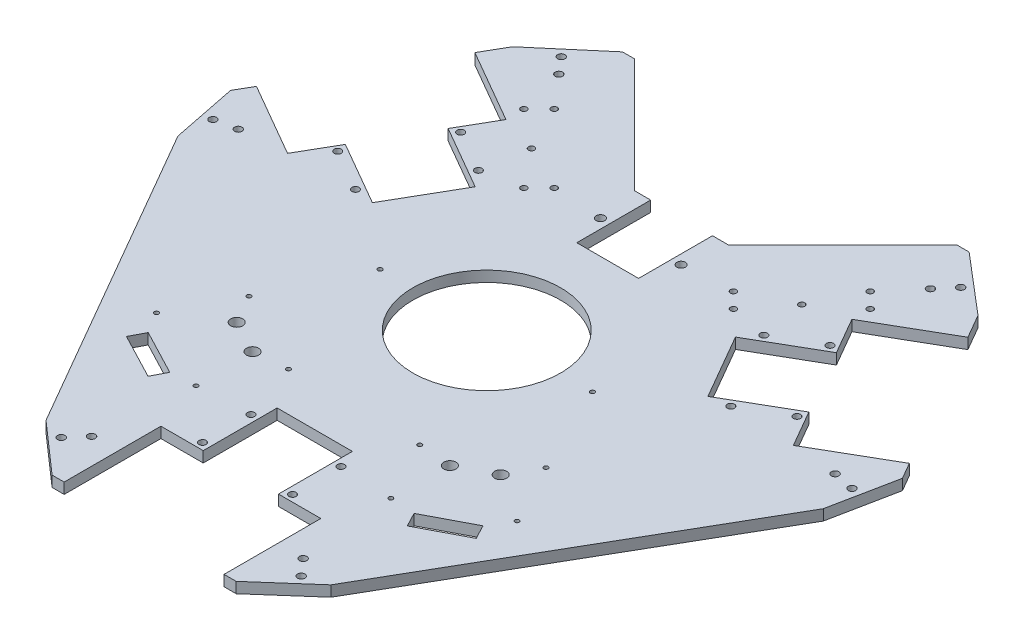
SolidWorks part; units mm, degrees
note: '?' marks a value the reader was unsure of.
material "1060 合金"
ref_plane "前视基准面" through (0, 0, 0) normal (0, 0, 1) x (1, 0, 0)
ref_plane "上视基准面" through (0, 0, 0) normal (0, 1, 0) x (1, 0, 0)
ref_plane "右视基准面" through (0, 0, 0) normal (1, 0, 0) x (0, 0, -1)
sketch "草图1" plane through (0, 0, 0) normal (0, 1, 0) x (1, 0, 0)
  line L1 (0, 0) -> (0, 227.8132) construction
  line L6 (0, 0) -> (-213.2068, 123.095) construction
  line L16 (-173.1806, 192.4224) -> (-250, 59.3672)
  line L17 (-250, 59.3672) -> (-68.5, -255) construction
  line L19 (250, 59.3672) -> (68.5, -255) construction
  line L20 (173.1806, 192.4224) -> (250, 59.3672)
  line L21 (-129, 230) -> (129, 230)
  line L22 (-250, 59.3672) -> (-240.171, 10.3428)
  line L23 (-250, -255) -> (250, -255) construction
  line L24 (-250, -255) -> (-250, 245) construction
  line L25 (-250, 245) -> (250, 245) construction
  line L26 (250, -255) -> (250, 245) construction
  line L27 (-250, -255) -> (250, 245) construction
  line L28 (-250, 245) -> (250, -255) construction
  line L29 (-240.171, 10.3428) -> (-106.0418, -221.9756)
  line L30 (-68.5, -255) -> (-106.0418, -221.9756)
  line L31 (68.5, -255) -> (106.0418, -221.9756)
  line L32 (240.171, 10.3428) -> (106.0418, -221.9756)
  line L33 (250, 59.3672) -> (240.171, 10.3428)
  line L34 (-173.1806, 192.4224) -> (-129, 230)
  line L35 (173.1806, 192.4224) -> (129, 230)
  line L36 (0, 0) -> (0, 164.1465) construction
  line L37 (-144.4826, 115.7487) -> (-128.7326, 143.0285) construction
  line L38 (-188.2326, 39.9715) -> (-242.9568, 71.5665) construction
  line L39 (-188.2326, 39.9715) -> (-172.4826, 67.2513) construction
  line L40 (-242.9568, 71.5665) -> (-183.4568, 174.6235) construction
  line L41 (-128.7326, 143.0285) -> (-183.4568, 174.6235) construction
  line L42 (-188.2326, 39.9715) -> (-183.4568, 174.6235) construction
  line L43 (-242.9568, 71.5665) -> (-128.7326, 143.0285) construction
  line L44 (-124.8513, 39.7513) -> (-172.4826, 67.2513) construction
  line L45 (-124.8513, 39.7513) -> (-96.8513, 88.2487) construction
  line L46 (-178.0961, 171.5285) -> (-237.5961, 68.4715) construction
  line L47 (-96.8513, 88.2487) -> (-144.4826, 115.7487) construction
  line L48 (-124.8513, 39.7513) -> (-144.4826, 115.7487) construction
  line L49 (-172.4826, 67.2513) -> (-96.8513, 88.2487) construction
  line L53 (-68.5, -255) -> (68.5, -255)
  circle A0 centre (0, 0) radius 55
  point P9 (-185.8447, 107.2975)
  point P10 (-134.667, 77.75)
  point P21 (0, 0)
  point P24 (0, 0)
  point P29 (0, -5)
  point P63 (0, 0)
  dimension "D10" = 110
  dimension "D2" = 5
  dimension "D3" = 258
  dimension "D4" = 119
  dimension "D6" = 230
  dimension "D7" = 500
  dimension "D8" = 16
  dimension "D9" = 60
  dimension "D11" = 63.19
  dimension "D12" = 55
  dimension "D5" = 128
  dimension "D13" = 56
  dimension "D14" = 60
  dimension "D15" = 57
  dimension "D16" = 137
  dimension "D17" = 255
  dimension "D18" = 246.19
  dimension "D19" = 50
  dimension "D20" = 58
extrude "凸台-拉伸1" add sketch "草图1" along normal blind 8
ref_axis "基准轴1" through (0, 0, 0) along (0, 1, 0)?
sketch "草图34" plane through (0, 8, 0) normal (0, 1, 0) x (1, 0, 0)
  line L0 (0, 0) -> (-213.2068, 123.095) construction
  line L1 (-173.1806, 192.4224) -> (-250, 59.3672) construction
  line L2 (0, 0) -> (0, 102.0762) construction
  line L3 (-144.4826, 115.7487) -> (-128.7326, 143.0285)
  line L4 (-188.2326, 39.9715) -> (-242.9568, 71.5665)
  line L5 (-188.2326, 39.9715) -> (-172.4826, 67.2513)
  line L6 (-242.9568, 71.5665) -> (-183.4568, 174.6235)
  line L7 (-128.7326, 143.0285) -> (-183.4568, 174.6235)
  line L8 (-188.2326, 39.9715) -> (-183.4568, 174.6235) construction
  line L9 (-242.9568, 71.5665) -> (-128.7326, 143.0285) construction
  line L11 (-124.8513, 39.7513) -> (-172.4826, 67.2513)
  line L12 (-124.8513, 39.7513) -> (-96.8513, 88.2487)
  line L13 (172.4826, 67.2513) -> (188.2326, 39.9715)
  line L14 (-96.8513, 88.2487) -> (-144.4826, 115.7487)
  line L15 (-124.8513, 39.7513) -> (-144.4826, 115.7487) construction
  line L16 (-172.4826, 67.2513) -> (-96.8513, 88.2487) construction
  line L17 (128.7326, 143.0285) -> (183.4568, 174.6235)
  line L18 (128.7326, 143.0285) -> (144.4826, 115.7487)
  line L19 (183.4568, 174.6235) -> (242.9568, 71.5665)
  line L20 (188.2326, 39.9715) -> (242.9568, 71.5665)
  line L21 (96.8513, 88.2487) -> (144.4826, 115.7487)
  line L22 (96.8513, 88.2487) -> (124.8513, 39.7513)
  line L23 (124.8513, 39.7513) -> (172.4826, 67.2513)
  line L24 (0, 0) -> (213.2068, 123.095) construction
  line L25 (128.7326, 143.0285) -> (242.9568, 71.5665) construction
  line L26 (183.4568, 174.6235) -> (188.2326, 39.9715) construction
  line L27 (96.8513, 88.2487) -> (172.4826, 67.2513) construction
  line L28 (144.4826, 115.7487) -> (124.8513, 39.7513) construction
  line L29 (-28, -183) -> (-59.5, -183)
  line L30 (59.5, -183) -> (59.5, -255)
  line L31 (59.5, -183) -> (28, -183)
  line L32 (59.5, -246.19) -> (-59.5, -246.19) construction
  line L33 (-59.5, -183) -> (-59.5, -255)
  line L34 (28, -128) -> (28, -183)
  line L35 (28, -128) -> (-28, -128)
  line L36 (-28, -128) -> (-28, -183)
  line L37 (0, 0) -> (0, -246.19) construction
  line L38 (59.5, -183) -> (-59.5, -246.19) construction
  line L39 (59.5, -246.19) -> (-59.5, -183) construction
  line L40 (28, -128) -> (-28, -183) construction
  line L41 (28, -183) -> (-28, -128) construction
  line L43 (-59.5, -255) -> (59.5, -255)
  line L44 (-68.5, -255) -> (68.5, -255) construction
  point P7 (-185.8447, 107.2975)
  point P10 (-134.667, 77.75)
  point P18 (185.8447, 107.2975)
  point P19 (134.667, 77.75)
  point P33 (0, -214.595)
  point P34 (0, -155.5)
  point P43 (0, 0)
  dimension "D1" = 60
  dimension "D2" = 183
  dimension "D3" = 119
  dimension "D4" = 55
  dimension "D5" = 56
  dimension "D6" = 3
extrude "切除-拉伸7" cut sketch "草图34" against normal through all
sketch "草图36" plane through (0, 8, 0) normal (0, 1, 0) x (1, 0, 0)
  line L0 (-63, 0) -> (-116.2089, 30.7202)
  line L1 (-63, 0) -> (-31.5, 54.5596) construction
  line L2 (-108.7089, 43.7106) -> (-92.2089, 72.2894)
  line L3 (-31.5, 54.5596) -> (-84.7089, 85.2798)
  line L4 (-63, 0) -> (-84.7089, 85.2798) construction
  line L5 (-116.2089, 30.7202) -> (-31.5, 54.5596) construction
  line L6 (-108.7089, 43.7106) -> (-60.9051, 16.111)
  line L7 (-108.7089, 43.7106) -> (-92.2089, 72.2894)
  line L8 (-60.9051, 16.111) -> (-44.4051, 44.6899) construction
  line L9 (-92.2089, 72.2894) -> (-44.4051, 44.6899)
  line L10 (-108.7089, 43.7106) -> (-44.4051, 44.6899) construction
  line L11 (-60.9051, 16.111) -> (-92.2089, 72.2894) construction
  line L12 (-108.7089, 43.7106) -> (-92.2089, 72.2894)
  line L13 (-84.7089, 85.2798) -> (-80.4589, 92.641)
  line L14 (31.5, 54.5596) -> (84.7089, 85.2798)
  line L15 (92.2089, 72.2894) -> (44.4051, 44.6899)
  line L16 (108.7089, 43.7106) -> (60.9051, 16.111)
  line L17 (63, 0) -> (116.2089, 30.7202)
  line L18 (31.5, -54.5596) -> (31.5, -116)
  line L19 (16.5, -116) -> (16.5, -60.8009)
  line L20 (-16.5, -116) -> (-16.5, -60.8009)
  line L21 (-31.5, -54.5596) -> (-31.5, -116)
  line L22 (92.2089, 72.2894) -> (108.7089, 43.7106)
  line L23 (116.2089, 30.7202) -> (120.4589, 23.359)
  line L24 (-31.5, -116) -> (-40, -116)
  line L25 (16.5, -116) -> (-16.5, -116)
  line L36 (144.4826, 115.7487) -> (128.7326, 143.0285)
  line L37 (126.0579, 222) -> (-126.0579, 222)
  line L38 (166.9439, 187.2246) -> (126.0579, 222)
  line L39 (241.5628, 57.9808) -> (166.9439, 187.2246)
  line L40 (232.5855, 13.2044) -> (241.5628, 57.9808)
  line L41 (99.7709, -216.8372) -> (232.5855, 13.2044)
  line L42 (65.4821, -247) -> (99.7709, -216.8372)
  line L43 (-65.4821, -247) -> (65.4821, -247)
  line L44 (-99.7709, -216.8372) -> (-65.4821, -247)
  line L45 (-232.5855, 13.2044) -> (-99.7709, -216.8372)
  line L46 (-241.5628, 57.9808) -> (-232.5855, 13.2044)
  line L47 (-166.9439, 187.2246) -> (-241.5628, 57.9808)
  line L48 (-126.0579, 222) -> (-166.9439, 187.2246)
  line L49 (126.0579, 222) -> (-126.0579, 222)
  line L50 (172.7415, 182.2935) -> (126.0579, 222)
  line L51 (128.7326, 143.0285) -> (183.4568, 174.6235)
  line L52 (232.5855, 13.2044) -> (241.319, 56.7645)
  line L53 (99.7709, -216.8372) -> (232.5855, 13.2044)
  line L54 (71.5, -241.7062) -> (99.7709, -216.8372)
  line L55 (183.4568, 174.6235) -> (173.1806, 192.4224)
  line L56 (-99.7709, -216.8372) -> (-71.5, -241.7062)
  line L57 (-232.5855, 13.2044) -> (-99.7709, -216.8372)
  line L58 (-241.319, 56.7645) -> (-232.5855, 13.2044)
  line L59 (173.1806, 192.4224) -> (129, 230)
  line L60 (-126.0579, 222) -> (-172.7415, 182.2935)
  line L61 (129, 230) -> (-129, 230)
  line L62 (-129, 230) -> (-173.1806, 192.4224)
  line L63 (-173.1806, 192.4224) -> (-183.4568, 174.6235)
  line L64 (-183.4568, 174.6235) -> (-128.7326, 143.0285)
  line L65 (-128.7326, 143.0285) -> (-144.4826, 115.7487)
  line L66 (-144.4826, 115.7487) -> (-96.8513, 88.2487)
  line L67 (-96.8513, 88.2487) -> (-124.8513, 39.7513)
  line L68 (-124.8513, 39.7513) -> (-172.4826, 67.2513)
  line L69 (-172.4826, 67.2513) -> (-188.2326, 39.9715)
  line L70 (-188.2326, 39.9715) -> (-242.9568, 71.5665)
  line L72 (-250, 59.3672) -> (-240.171, 10.3428)
  line L73 (-240.171, 10.3428) -> (-106.0418, -221.9756)
  line L74 (-106.0418, -221.9756) -> (-68.5, -255)
  line L75 (-248.9568, 61.1742) -> (-183.8403, 23.5792)
  line L76 (-183.8403, 23.5792) -> (-168.0903, 50.859)
  line L77 (-168.0903, 50.859) -> (-120.4589, 23.359)
  line L78 (-120.4589, 23.359) -> (-80.4589, 92.641)
  line L79 (-80.4589, 92.641) -> (-128.0903, 120.141)
  line L80 (-128.0903, 120.141) -> (-112.3403, 147.4208)
  line L81 (-112.3403, 147.4208) -> (-177.4568, 185.0158)
  line L82 (-241.319, 56.7645) -> (-183.8403, 23.5792)
  line L83 (-183.8403, 23.5792) -> (-168.0903, 50.859)
  line L84 (-168.0903, 50.859) -> (-120.4589, 23.359)
  line L85 (-120.4589, 23.359) -> (-116.2089, 30.7202)
  line L86 (-80.4589, 92.641) -> (-128.0903, 120.141)
  line L87 (-128.0903, 120.141) -> (-112.3403, 147.4208)
  line L88 (-112.3403, 147.4208) -> (-172.7415, 182.2935)
  line L90 (-59.5, -255) -> (-59.5, -183)
  line L91 (-59.5, -183) -> (-28, -183)
  line L92 (-28, -183) -> (-28, -128)
  line L93 (-28, -128) -> (28, -128)
  line L94 (28, -128) -> (28, -183)
  line L95 (28, -183) -> (59.5, -183)
  line L96 (59.5, -183) -> (59.5, -255)
  line L97 (-65.4821, -247) -> (65.4821, -247)
  line L98 (68.5, -255) -> (106.0418, -221.9756)
  line L99 (106.0418, -221.9756) -> (240.171, 10.3428)
  line L100 (240.171, 10.3428) -> (250, 59.3672)
  line L102 (242.9568, 71.5665) -> (188.2326, 39.9715)
  line L103 (188.2326, 39.9715) -> (172.4826, 67.2513)
  line L104 (172.4826, 67.2513) -> (124.8513, 39.7513)
  line L105 (124.8513, 39.7513) -> (96.8513, 88.2487)
  line L106 (96.8513, 88.2487) -> (144.4826, 115.7487)
  line L107 (144.4826, 115.7487) -> (128.7326, 143.0285)
  line L108 (128.7326, 143.0285) -> (183.4568, 174.6235)
  line L109 (183.4568, 174.6235) -> (173.1806, 192.4224)
  line L110 (173.1806, 192.4224) -> (129, 230)
  line L111 (129, 230) -> (-129, 230)
  line L112 (-129, 230) -> (-173.1806, 192.4224)
  line L113 (-173.1806, 192.4224) -> (-183.4568, 174.6235)
  line L114 (-183.4568, 174.6235) -> (-128.7326, 143.0285)
  line L115 (-128.7326, 143.0285) -> (-144.4826, 115.7487)
  line L116 (-144.4826, 115.7487) -> (-96.8513, 88.2487)
  line L117 (-96.8513, 88.2487) -> (-124.8513, 39.7513)
  line L118 (183.8403, 23.5792) -> (248.9568, 61.1742)
  line L119 (168.0903, 50.859) -> (183.8403, 23.5792)
  line L120 (120.4589, 23.359) -> (168.0903, 50.859)
  line L121 (80.4589, 92.641) -> (120.4589, 23.359)
  line L122 (128.0903, 120.141) -> (80.4589, 92.641)
  line L123 (112.3403, 147.4208) -> (128.0903, 120.141)
  line L124 (177.4568, 185.0158) -> (112.3403, 147.4208)
  line L125 (183.8403, 23.5792) -> (241.319, 56.7645)
  line L126 (168.0903, 50.859) -> (183.8403, 23.5792)
  line L127 (120.4589, 23.359) -> (168.0903, 50.859)
  line L128 (80.4589, 92.641) -> (84.7089, 85.2798)
  line L129 (128.0903, 120.141) -> (80.4589, 92.641)
  line L130 (112.3403, 147.4208) -> (128.0903, 120.141)
  line L131 (172.7415, 182.2935) -> (112.3403, 147.4208)
  line L132 (-124.8513, 39.7513) -> (-172.4826, 67.2513)
  line L133 (-172.4826, 67.2513) -> (-188.2326, 39.9715)
  line L134 (-188.2326, 39.9715) -> (-242.9568, 71.5665)
  line L136 (-250, 59.3672) -> (-240.171, 10.3428)
  line L137 (-240.171, 10.3428) -> (-106.0418, -221.9756)
  line L138 (-106.0418, -221.9756) -> (-68.5, -255)
  line L140 (-59.5, -255) -> (-59.5, -183)
  line L141 (-59.5, -183) -> (-28, -183)
  line L142 (-28, -183) -> (-28, -128)
  line L143 (-28, -128) -> (28, -128)
  line L144 (28, -128) -> (28, -183)
  line L145 (28, -183) -> (59.5, -183)
  line L146 (59.5, -183) -> (59.5, -255)
  line L148 (68.5, -255) -> (106.0418, -221.9756)
  line L149 (106.0418, -221.9756) -> (240.171, 10.3428)
  line L150 (240.171, 10.3428) -> (250, 59.3672)
  line L152 (242.9568, 71.5665) -> (188.2326, 39.9715)
  line L153 (188.2326, 39.9715) -> (172.4826, 67.2513)
  line L154 (172.4826, 67.2513) -> (124.8513, 39.7513)
  line L155 (124.8513, 39.7513) -> (96.8513, 88.2487)
  line L156 (96.8513, 88.2487) -> (144.4826, 115.7487)
  line L160 (71.5, -255) -> (71.5, -171)
  line L161 (71.5, -171) -> (40, -171)
  line L162 (40, -171) -> (40, -116)
  line L163 (40, -116) -> (-40, -116)
  line L164 (-40, -116) -> (-40, -171)
  line L165 (-40, -171) -> (-71.5, -171)
  line L166 (-71.5, -171) -> (-71.5, -255)
  line L167 (71.5, -241.7062) -> (71.5, -171)
  line L168 (71.5, -171) -> (40, -171)
  line L169 (40, -171) -> (40, -116)
  line L170 (40, -116) -> (31.5, -116)
  line L171 (-40, -116) -> (-40, -171)
  line L172 (-40, -171) -> (-71.5, -171)
  line L173 (-71.5, -171) -> (-71.5, -241.7062)
  line L190 (-242.9568, 71.5665) -> (-250, 59.3672)
  line L191 (-242.9568, 71.5665) -> (-250, 59.3672)
  line L192 (250, 59.3672) -> (242.9568, 71.5665)
  line L193 (250, 59.3672) -> (242.9568, 71.5665)
  line L194 (-68.5, -255) -> (-59.5, -255)
  line L195 (-68.5, -255) -> (-59.5, -255)
  line L196 (59.5, -255) -> (68.5, -255)
  line L197 (59.5, -255) -> (68.5, -255)
  circle A0 centre (0, 0) radius 55 construction
  circle A1 centre (0, 0) radius 55
  circle A2 centre (0, 0) radius 63
  arc A3 (-44.4051, 44.6899) -> (-60.9051, 16.111) centre (0, 0) ccw
  arc A4 (-63, 0) -> (-31.5, -54.5596) centre (0, 0) ccw
  arc A5 (31.5, 54.5596) -> (-31.5, 54.5596) centre (0, 0) ccw
  arc A6 (60.9051, 16.111) -> (44.4051, 44.6899) centre (0, 0) ccw
  arc A7 (31.5, -54.5596) -> (63, 0) centre (0, 0) ccw
  arc A8 (-16.5, -60.8009) -> (16.5, -60.8009) centre (0, 0) ccw
  point P84 (-73.8545, 42.6399)
  point P85 (-76.557, 44.2002)
  point P111 (0, 0)
  dimension "D7" = 15
  dimension "D8" = 3
  dimension "D1" = 8
  dimension "D2" = 12
  dimension "D3" = 8
  dimension "D4" = 12
  dimension "D5" = 12
  dimension "D6" = 0
extrude "凸台-拉伸4" [suppressed] add sketch "草图36" along normal blind 10 separate body
hole_wizard "M5 间隙孔1" positions "草图3" profile "草图4" hole size "M5" standard "GB" end condition through all
sketch "草图3" plane through (0, 0, 0) normal (0, -1, 0) x (-1, 0, 0)
  line L0 (0, 0) -> (211.6387, 122.1897) construction
  line L1 (170.9025, 59.9881) -> (139.7256, 41.9881) construction
  line L2 (170.9025, 59.9881) -> (137.4025, 118.0119) construction
  line L3 (139.7256, 41.9881) -> (106.2256, 100.0119) construction
  line L4 (137.4025, 118.0119) -> (106.2256, 100.0119) construction
  line L19 (144.4826, 115.7487) -> (128.7326, 143.0285) construction
  point P5 (106.2256, 100.0119)
  point P7 (137.4025, 118.0119)
  point P9 (139.7256, 41.9881)
  point P11 (170.9025, 59.9881)
  dimension "D1" = 67
  dimension "D2" = 5
  dimension "D3" = 36
sketch "草图4" plane through (-106.2256, 0, -100.0119) normal (1, 0, 0) x (0, 0, -1)
  line L0 (0, 0) -> (0, 8)
  line L1 (0, 8) -> (2.65, 8)
  line L2 (2.65, 8) -> (2.65, 0)
  line L5 (2.65, 0) -> (0, 0)
  line L11 (0, -6.35) -> (0, 107.95) construction
  dimension "通孔孔直径" = 5.3
  dimension "通孔孔深度" = 8
pattern_circular "阵列(圆周)5" count 3 over 360 about axis through (0, 0, 0) along (0, 1, 0) of "M5 间隙孔1"
sketch "草图5" plane through (0, 8, 0) normal (0, 1, 0) x (1, 0, 0)
  line L0 (-129, 230) -> (129, 230) construction
  line L1 (129, 230) -> (-121.0813, 230) construction
  line L2 (0, 0) -> (0, 310.7708) construction
  line L3 (120, 230) -> (35, 145)
  line L4 (35, 145) -> (-35, 145)
  line L5 (-120, 230) -> (-35, 145)
  line L7 (129, 230) -> (-129, 230) construction
  point P10 (0, 145)
  dimension "D1" = 45
  dimension "D2" = 85
  dimension "D3" = 240
extrude "切除-拉伸2" cut sketch "草图5" against normal through all and the other way through all
sketch "草图7" plane through (0, 8, 0) normal (0, 1, 0) x (1, 0, 0)
  line L1 (0, 0) -> (0, 218.1098) construction
  line L3 (-23, 230) -> (23, 230)
  line L4 (-23, 230) -> (-23, 90)
  line L5 (-23, 90) -> (23, 90)
  line L6 (23, 230) -> (23, 90)
  line L7 (-23, 230) -> (23, 90) construction
  line L8 (-23, 90) -> (23, 230) construction
  point P7 (0, 160)
  dimension "D1" = 90
  dimension "D2" = 46
extrude "切除-拉伸4" cut sketch "草图7" against normal through all
hole_wizard "M6 间隙孔1" positions "草图8" profile "草图9" hole size "M6" standard "GB" end condition up to next
sketch "草图8" plane through (0, 8, 0) normal (0, 1, 0) x (1, 0, 0)
  line L0 (0, 0) -> (0, 212.5269) construction
  line L3 (-23, 90) -> (23, 90) construction
  point P2 (30, 114.64)
  point P4 (-30, 114.64)
  dimension "D1" = 24.64
  dimension "D2" = 60
sketch "草图9" plane through (30, 8, -114.64) normal (1, 0, 0) x (0, 0, 1)
  line L0 (0, 0) -> (0, 8)
  line L1 (0, 8) -> (3.2, 8)
  line L2 (3.2, 8) -> (3.2, 0)
  line L5 (3.2, 0) -> (0, 0)
  line L11 (0, -6.35) -> (0, 107.95) construction
  dimension "通孔孔直径" = 6.4
  dimension "通孔孔深度" = 8
sketch "草图12" plane through (0, 8, 0) normal (0, 1, 0) x (1, 0, 0)
  line L0 (0, -0.36) -> (0, -5) construction
  line L2 (-79, -0.36) -> (79, -0.36) construction
  circle A0 centre (30, 114.64) radius 3.2 construction
  point P0 (-79, -0.36)
  point P9 (79, -0.36)
  dimension "D1" = 158
  dimension "D2" = 115
hole_wizard "电磁铁M4 螺纹孔1" positions "草图14" profile "草图13" tap size "M4" standard "GB" end condition through all
sketch "草图14" plane through (0, 8, 0) normal (0, 1, 0) x (1, 0, 0)
  point P0 (-79, -0.36)
  point P3 (79, -0.36)
sketch "草图13" plane through (-79, 8, 0.36) normal (1, 0, 0) x (0, 0, 1)
  line L0 (0, 0) -> (0, 8)
  line L1 (0, 8) -> (1.65, 8)
  line L2 (1.65, 8) -> (1.65, 0)
  line L5 (1.65, 0) -> (0, 0)
  line L11 (0, -6.35) -> (0, 107.95) construction
  dimension "螺纹线主直径" = 3.3
  dimension "通孔螺纹孔钻头深度" = 8
hole_wizard "电池座 M3 间隙孔1" positions "草图19" profile "草图20" hole size "M3" standard "GB" end condition up to next
sketch "草图19" plane through (0, 0, 0) normal (0, -1, 0) x (-1, 0, 0)
  line L0 (-79.6771, -82.5804) -> (-131.6224, -181.8059) construction
  line L4 (-72.5, -143.9036) -> (-48.8464, -98.7205)
  line L5 (-72.5, -143.9036) -> (-134.1615, -111.6233)
  line L6 (-134.1615, -111.6233) -> (-110.5079, -66.4403)
  line L7 (-48.8464, -98.7205) -> (-110.5079, -66.4403)
  line L8 (-72.5, -143.9036) -> (-110.5079, -66.4403) construction
  line L9 (-134.1615, -111.6233) -> (-48.8464, -98.7205) construction
  line L15 (0, 0) -> (0, -144.4451) construction
  line L18 (-73.4425, -100.8566) -> (-98.2488, -87.8703)
  line L19 (-102.8678, -223.9044) -> (-72.6341, -166.152)
  line L20 (-102.8678, -223.9044) -> (-182.6026, -182.1627)
  line L21 (-72.6341, -166.152) -> (-152.3688, -124.4103)
  line L22 (-182.6026, -182.1627) -> (-152.3688, -124.4103)
  line L23 (-102.8678, -223.9044) -> (-152.3688, -124.4103) construction
  line L24 (-72.6341, -166.152) -> (-182.6026, -182.1627) construction
  point P7 (-110.5079, -66.4403)
  point P10 (-72.5, -143.9036)
  point P11 (-134.1615, -111.6233)
  point P12 (-48.8464, -98.7205)
  dimension "D1" = 69.6
  dimension "D2" = 51
  dimension "D3" = 90
  dimension "D4" = 145
  dimension "D5" = 61
  dimension "D6" = 13.3
  dimension "D7" = 28
sketch "草图20" plane through (110.5079, 0, 66.4403) normal (1, 0, 0) x (0, 0, -1)
  line L0 (0, 0) -> (0, 8.001)
  line L1 (0, 8.001) -> (1.6, 8.001)
  line L2 (1.6, 8.001) -> (1.6, 0)
  line L5 (1.6, 0) -> (0, 0)
  line L11 (0, -6.35) -> (0, 107.95) construction
  dimension "通孔孔直径" = 3.2
  dimension "通孔孔深度" = 8.001
sketch "草图37" plane through (0, 8, 0) normal (0, 1, 0) x (1, 0, 0)
  line L0 (102.8678, -223.9044) -> (182.6026, -182.1627)
  line L1 (102.8678, -223.9044) -> (72.6341, -166.152)
  line L2 (182.6026, -182.1627) -> (152.3688, -124.4103)
  line L3 (72.6341, -166.152) -> (152.3688, -124.4103)
extrude "切除-拉伸8" [suppressed] cut sketch "草图37" along normal up to next
hole_wizard "Ø9.0 (9) 直径孔1" positions "草图23" profile "草图22" hole size "Ø9.0" standard "GB" end condition through all
sketch "草图23" [suppressed] plane through (0, 0, 0) normal (0, -1, 0) x (-1, 0, 0)
  point P0 (-98.2488, -87.8703)
  point P3 (-73.4425, -100.8566)
sketch "草图22" plane through (98.2488, 0, 87.8703) normal (1, 0, 0) x (0, 0, -1)
  line L0 (0, 0) -> (0, 8)
  line L1 (0, 8) -> (4.5, 8)
  line L2 (4.5, 8) -> (4.5, 0)
  line L5 (4.5, 0) -> (0, 0)
  line L11 (0, -6.35) -> (0, 107.95) construction
  dimension "通孔孔直径" = 9
  dimension "通孔孔深度" = 8
sketch "草图21" plane through (0, 0, 0) normal (0, -1, 0) x (1, 0, 0)
  line L1 (90.9039, 144.992) -> (96.4695, 155.6233)
  line L2 (90.9039, 144.992) -> (124.5697, 127.3677)
  line L3 (124.5697, 127.3677) -> (130.1353, 137.999)
  line L4 (96.4695, 155.6233) -> (130.1353, 137.999)
  line L5 (90.9039, 144.992) -> (130.1353, 137.999) construction
  line L6 (124.5697, 127.3677) -> (96.4695, 155.6233) construction
  line L7 (134.1615, 111.6233) -> (72.5, 143.9036) construction
  line L8 (103.3308, 127.7634) -> (122.1059, 163.6275) construction
  point P0 (110.5196, 141.4955)
  dimension "D1" = 38
  dimension "D2" = 12
  dimension "D3" = 9.5
extrude "切除-拉伸6" cut sketch "草图21" against normal blind 10
mirror "镜向1" about plane through (0, 0, 0) normal (1, 0, 0) of "Ø9.0 (9) 直径孔1", "电池座 M3 间隙孔1", "切除-拉伸6"
fillet "圆角1" [suppressed] radius 4
mirror "镜向3" about plane through (0, 0, 0) normal (1, 0, 0) of bodies 118
hole_wizard "立柱 M5 间隙孔3" positions "草图46" profile "草图45" hole size "M5" standard "GB" end condition up to next
sketch "草图46" plane through (0, 0, 0) normal (0, -1, 0) x (-1, 0, 0)
  point P0 (-237.7798, 34.0253)
  point P3 (-222.092, 37.1706)
  point P6 (-138.2797, 191.9129)
  point P9 (-148.646, 204.1006)
  point P12 (-89.2984, -227.3814)
  point P15 (-78.7306, -215.368)
sketch "草图45" plane through (237.7798, 0, -34.0253) normal (1, 0, 0) x (0, 0, -1)
  line L0 (0, 0) -> (0, 8.001)
  line L1 (0, 8.001) -> (2.75, 8.001)
  line L2 (2.75, 8.001) -> (2.75, 0)
  line L5 (2.75, 0) -> (0, 0)
  line L11 (0, -6.35) -> (0, 107.95) construction
  dimension "通孔孔直径" = 5.5
  dimension "通孔孔深度" = 8.001
mirror "镜向4" about plane through (0, 0, 0) normal (1, 0, 0) of "立柱 M5 间隙孔3"
hole_wizard "M4 间隙孔1" positions "草图48" profile "草图47" hole size "M4" standard "GB" end condition up to next
sketch "草图48" plane through (0, 0, 0) normal (0, -1, 0) x (-1, 0, 0)
  point P0 (128.8807, 156.5059)
  point P3 (117.567, 167.8196)
  point P6 (66.6553, 116.908)
  point P9 (77.969, 105.5942)
  point P12 (100.5964, 133.8785)
sketch "草图47" plane through (-128.8807, 0, -156.5059) normal (1, 0, 0) x (0, 0, -1)
  line L0 (0, 0) -> (0, 8.001)
  line L1 (0, 8.001) -> (2.25, 8.001)
  line L2 (2.25, 8.001) -> (2.25, 0)
  line L5 (2.25, 0) -> (0, 0)
  line L11 (0, -6.35) -> (0, 107.95) construction
  dimension "通孔孔直径" = 4.5
  dimension "通孔孔深度" = 8.001
sketch "草图50" plane through (0, 8, 0) normal (0, 1, 0) x (1, 0, 0)
  line L0 (-200.4618, -8.4355) -> (-172.5002, -56.8663)
  line L2 (-162.2301, -57.0686) -> (-138.853, -20.0286)
  line L3 (-142.6273, -10.9687) -> (-193.966, 0.4221)
  line L4 (-240.171, 10.3428) -> (-106.0418, -221.9756) construction
  arc A0 (-172.5002, -56.8663) -> (-162.2301, -57.0686) centre (-167.3041, -53.8663) ccw
  arc A1 (-200.4618, -8.4355) -> (-193.966, 0.4221) centre (-195.2656, -5.4355) cw
  arc A2 (-138.853, -20.0286) -> (-142.6273, -10.9687) centre (-143.927, -16.8263) ccw
  dimension "D2" = 6
  dimension "D1" = 25
extrude "切除-拉伸9" [suppressed] cut sketch "草图50" against normal through all
mirror "镜向5" about plane through (0, 0, 0) normal (1, 0, 0) of "切除-拉伸9", "M4 间隙孔1"
